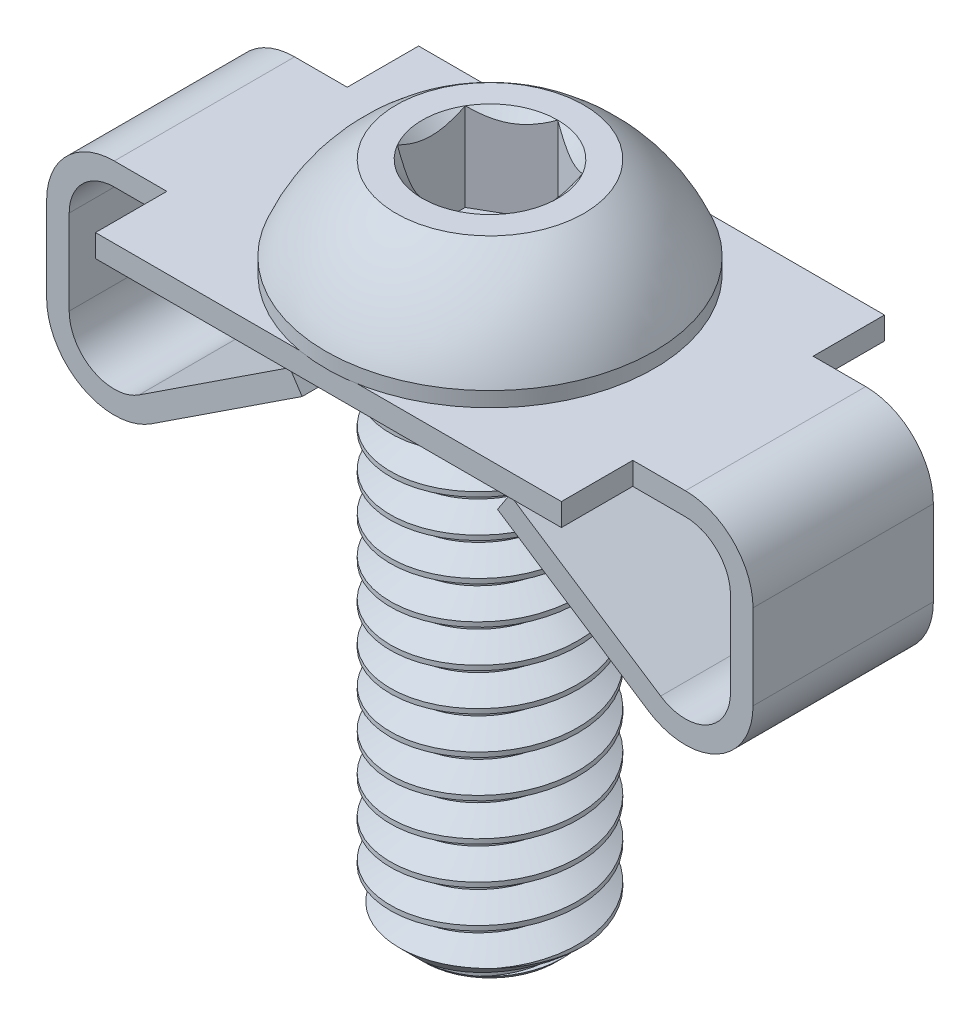
SolidWorks part; units mm, degrees
ref_plane "Front Plane" through (0, 0, 0) normal (0, 0, 1) x (1, 0, 0)
ref_plane "Top Plane" through (0, 0, 0) normal (0, 1, 0) x (1, 0, 0)
ref_plane "Right Plane" through (0, 0, 0) normal (1, 0, 0) x (0, 0, -1)
sketch "Sketch1" plane through (0, 0, 0) normal (0, 1, 0) x (1, 0, 0)
  circle A0 centre (0, 0) radius 3.175
  point P3 (-3.175, 0)
  dimension "D1" = 6.35
extrude "Boss-Extrude1" add sketch "Sketch1" against normal blind 19.05
sketch "Sketch2" plane through (0, -19.05, 0) normal (0, -1, 0) x (1, 0, 0)
  circle A1 centre (0, 0) radius 3.175
  circle A2 centre (0, 0) radius 3.175
  point P0 (0, -3.175)
  dimension "D1" = 0
curve "Helix/Spiral1" pitch 1.27 height 20.32 turns 16
sketch "Sketch3" plane through (0, 0, 0) normal (1, 0, 0) x (0, 0, -1)
  line L0 (3.3125, -18.9706) -> (2.2126, -19.6056) construction
  line L1 (2.2126, -19.6056) -> (3.3125, -20.2406) construction
  line L2 (3.3125, -20.2406) -> (3.3125, -18.9706) construction
  line L3 (2.3501, -19.5262) -> (2.3501, -19.685) construction
  line L4 (3.175, -19.05) -> (3.175, -20.1612) construction
  line L5 (2.2126, -19.6056) -> (2.3501, -19.6056) construction
  line L6 (3.175, -19.6056) -> (3.3125, -19.6056) construction
  line L8 (2.2126, -19.6056) -> (-3.175, -19.6056) construction
  line L9 (2.3501, -19.5262) -> (3.2437, -19.0103)
  line L10 (2.3501, -19.5262) -> (2.3501, -19.685)
  line L11 (2.3501, -19.685) -> (3.2437, -20.2009)
  line L12 (3.2437, -20.2009) -> (3.2437, -19.0103)
  line L14 (-3.175, -19.6056) -> (-3.175, -18.3356) construction
  line L15 (-3.175, -18.3356) -> (-3.175, -17.0656) construction
  line L16 (-3.175, -17.0656) -> (-3.175, -15.7956) construction
  line L17 (-3.175, -15.7956) -> (-3.175, -14.5256) construction
  line L18 (-3.175, 0) -> (-3.175, -19.05) construction
  point P15 (3.2437, -19.6056)
  dimension "D1" = 1.27
  dimension "D2" = 0.1588
sweep "Cut-Sweep1" cut profiles "Sketch3" path "Helix/Spiral1"
sketch "Sketch4" plane through (0, -19.05, 0) normal (0, -1, 0) x (1, 0, 0)
  circle A0 centre (0, 0) radius 2.2126
extrude "Cut-Extrude1" cut sketch "Sketch4" against normal blind 1.27 draft 45 flip side to cut
sketch "Sketch5" plane through (0, 0, 0) normal (0, 0, 1) x (1, 0, 0)
  line L0 (0, 0) -> (0, 3.3528)
  line L1 (0, 0) -> (0, -19.05) construction
  line L2 (0, 3.3528) -> (-3.175, 3.3528)
  line L3 (-5.5499, 0.5029) -> (-5.5499, 0)
  line L4 (-5.5499, 0) -> (0, 0)
  arc A0 (-3.175, 3.3528) -> (-5.5499, 0.5029) centre (0, -1.7075) ccw
  dimension "D1" = 3.3528
  dimension "D2" = 11.0998
  dimension "D3" = 0.5029
revolve "Revolve1" add sketch "Sketch5" angle 360 mid plane about L1
sketch "Sketch6" plane through (0, 3.3528, 0) normal (0, 1, 0) x (1, 0, 0)
  line L1 (0, 2.2914) -> (-1.9844, 1.1457)
  line L2 (-1.9844, 1.1457) -> (-1.9844, -1.1457)
  line L3 (-1.9844, -1.1457) -> (0, -2.2914)
  line L4 (0, -2.2914) -> (1.9844, -1.1457)
  line L5 (1.9844, -1.1457) -> (1.9844, 1.1457)
  line L6 (1.9844, 1.1457) -> (0, 2.2914)
  circle A0 centre (0, 0) radius 1.9844 construction
extrude "Cut-Extrude2" cut sketch "Sketch6" against normal blind 2.9766
sketch "Sketch7" plane through (0, 3.3528, 0) normal (0, 1, 0) x (1, 0, 0)
  circle A0 centre (0, 0) radius 2.2914
extrude "Cut-Extrude3" cut sketch "Sketch7" against normal blind 2.9766 draft 45
sketch "Sketch8" plane through (0, 0, 0) normal (0, 0, 1) x (1, 0, 0)
  line L0 (-9.652, 0) -> (9.652, 0)
  line L1 (0, 0) -> (0, -31.7459) construction
  line L2 (-11.938, -2.286) -> (-11.938, -5.1562)
  line L3 (-8.3972, -7.067) -> (-3.302, -3.7211)
  line L4 (-3.302, -3.7211) -> (-3.7203, -3.0842)
  line L5 (-3.7203, -3.0842) -> (-8.8155, -6.4301)
  line L6 (-11.176, -5.1562) -> (-11.176, -2.286)
  line L7 (-9.652, -0.762) -> (9.652, -0.762)
  line L8 (11.176, -5.1562) -> (11.176, -2.286)
  line L9 (3.7203, -3.0842) -> (8.8155, -6.4301)
  line L10 (3.302, -3.7211) -> (3.7203, -3.0842)
  line L11 (8.3972, -7.067) -> (3.302, -3.7211)
  line L12 (11.938, -2.286) -> (11.938, -5.1562)
  line L13 (-11.938, -3.7211) -> (-3.302, -3.7211) construction
  arc A0 (-9.652, 0) -> (-11.938, -2.286) centre (-9.652, -2.286) ccw
  arc A1 (-11.938, -5.1562) -> (-8.3972, -7.067) centre (-9.652, -5.1562) ccw
  arc A2 (-8.8155, -6.4301) -> (-11.176, -5.1562) centre (-9.652, -5.1562) cw
  arc A3 (-11.176, -2.286) -> (-9.652, -0.762) centre (-9.652, -2.286) cw
  arc A4 (11.176, -2.286) -> (9.652, -0.762) centre (9.652, -2.286) ccw
  arc A5 (8.8155, -6.4301) -> (11.176, -5.1562) centre (9.652, -5.1562) ccw
  arc A6 (11.938, -5.1562) -> (8.3972, -7.067) centre (9.652, -5.1562) cw
  arc A7 (9.652, 0) -> (11.938, -2.286) centre (9.652, -2.286) cw
  dimension "D1" = 7.4422
  dimension "D2" = 23.876
  dimension "D3" = 2.286
  dimension "D4" = 0.127
  dimension "D5" = 0.762
extrude "Boss-Extrude2" add sketch "Sketch8" against normal mid plane 10.922 separate body
sketch "Sketch9" plane through (0, 0, 0) normal (0, 1, 0) x (-1, 0, 0)
  circle A1 centre (0, 0) radius 3.175
  circle A2 centre (0, 0) radius 3.175
  dimension "D1" = 0
extrude "Cut-Extrude4" cut sketch "Sketch9" against normal through all
sketch "Sketch10" plane through (0, 0, 0) normal (0, 0, 1) x (1, 0, 0)
  line L0 (-7.874, 0) -> (-7.874, -0.762)
  line L1 (0, -0.762) -> (0, 0) construction
  line L2 (7.874, 0) -> (7.874, -0.762)
  line L3 (7.874, -0.762) -> (9.652, -0.762)
  line L4 (-7.874, 0) -> (-9.652, 0)
  line L5 (-9.652, -0.762) -> (9.652, -0.762) construction
  line L12 (-11.938, -2.286) -> (-11.938, -5.1562)
  line L13 (-8.3972, -7.067) -> (-3.302, -3.7211)
  line L14 (-3.302, -3.7211) -> (-3.7203, -3.0842)
  line L15 (-3.7203, -3.0842) -> (-8.8155, -6.4301)
  line L16 (-11.176, -5.1562) -> (-11.176, -2.286)
  line L17 (-9.652, -0.762) -> (9.652, -0.762)
  line L18 (11.176, -2.286) -> (11.176, -5.1562)
  line L19 (8.8155, -6.4301) -> (3.7203, -3.0842)
  line L20 (3.7203, -3.0842) -> (3.302, -3.7211)
  line L21 (3.302, -3.7211) -> (8.3972, -7.067)
  line L22 (11.938, -5.1562) -> (11.938, -2.286)
  line L23 (9.652, 0) -> (-9.652, 0)
  line L24 (-11.938, -2.286) -> (-11.938, -5.1562)
  line L25 (-8.3972, -7.067) -> (-3.302, -3.7211)
  line L26 (-3.302, -3.7211) -> (-3.7203, -3.0842)
  line L27 (-3.7203, -3.0842) -> (-8.8155, -6.4301)
  line L28 (-11.176, -5.1562) -> (-11.176, -2.286)
  line L29 (-9.652, -0.762) -> (-7.874, -0.762)
  line L30 (11.176, -2.286) -> (11.176, -5.1562)
  line L31 (8.8155, -6.4301) -> (3.7203, -3.0842)
  line L32 (3.7203, -3.0842) -> (3.302, -3.7211)
  line L33 (3.302, -3.7211) -> (8.3972, -7.067)
  line L34 (11.938, -5.1562) -> (11.938, -2.286)
  line L35 (9.652, 0) -> (7.874, 0)
  arc A8 (-9.652, 0) -> (-11.938, -2.286) centre (-9.652, -2.286) ccw
  arc A9 (-11.938, -5.1562) -> (-8.3972, -7.067) centre (-9.652, -5.1562) ccw
  arc A10 (-11.176, -5.1562) -> (-8.8155, -6.4301) centre (-9.652, -5.1562) ccw
  arc A11 (-9.652, -0.762) -> (-11.176, -2.286) centre (-9.652, -2.286) ccw
  arc A12 (11.176, -2.286) -> (9.652, -0.762) centre (9.652, -2.286) ccw
  arc A13 (8.8155, -6.4301) -> (11.176, -5.1562) centre (9.652, -5.1562) ccw
  arc A14 (8.3972, -7.067) -> (11.938, -5.1562) centre (9.652, -5.1562) ccw
  arc A15 (11.938, -2.286) -> (9.652, 0) centre (9.652, -2.286) ccw
  arc A16 (-9.652, 0) -> (-11.938, -2.286) centre (-9.652, -2.286) ccw
  arc A17 (-11.938, -5.1562) -> (-8.3972, -7.067) centre (-9.652, -5.1562) ccw
  arc A18 (-11.176, -5.1562) -> (-8.8155, -6.4301) centre (-9.652, -5.1562) ccw
  arc A19 (-9.652, -0.762) -> (-11.176, -2.286) centre (-9.652, -2.286) ccw
  arc A20 (11.176, -2.286) -> (9.652, -0.762) centre (9.652, -2.286) ccw
  arc A21 (8.8155, -6.4301) -> (11.176, -5.1562) centre (9.652, -5.1562) ccw
  arc A22 (8.3972, -7.067) -> (11.938, -5.1562) centre (9.652, -5.1562) ccw
  arc A23 (11.938, -2.286) -> (9.652, 0) centre (9.652, -2.286) ccw
  dimension "D2" = 15.748
  dimension "D1" = 0
extrude "Cut-Extrude5" cut sketch "Sketch10" along normal through all from offset 3.048
mirror "Mirror1" about plane through (0, 0, 0) normal (0, 0, 1) of "Cut-Extrude5"
equation "\"D3@Helix/Spiral1\" = \"D4@Helix/Spiral1\" + \"D1@Boss-Extrude1\""
equation "\"D1@Sketch3\" = \"D4@Helix/Spiral1\""
equation "\"D2@Sketch3\" = \"D1@Sketch3\" / 8"
equation "\"D1@Cut-Extrude1\" = \"D4@Helix/Spiral1\""
equation "\"D3@Sketch5\" = \"D1@Sketch5\" * 0.15"
equation "\"D1@Cut-Extrude2\" = \"D1@Sketch6\" * 3/4"
equation "\"D1@Cut-Extrude3\" = \"D1@Cut-Extrude2\""
